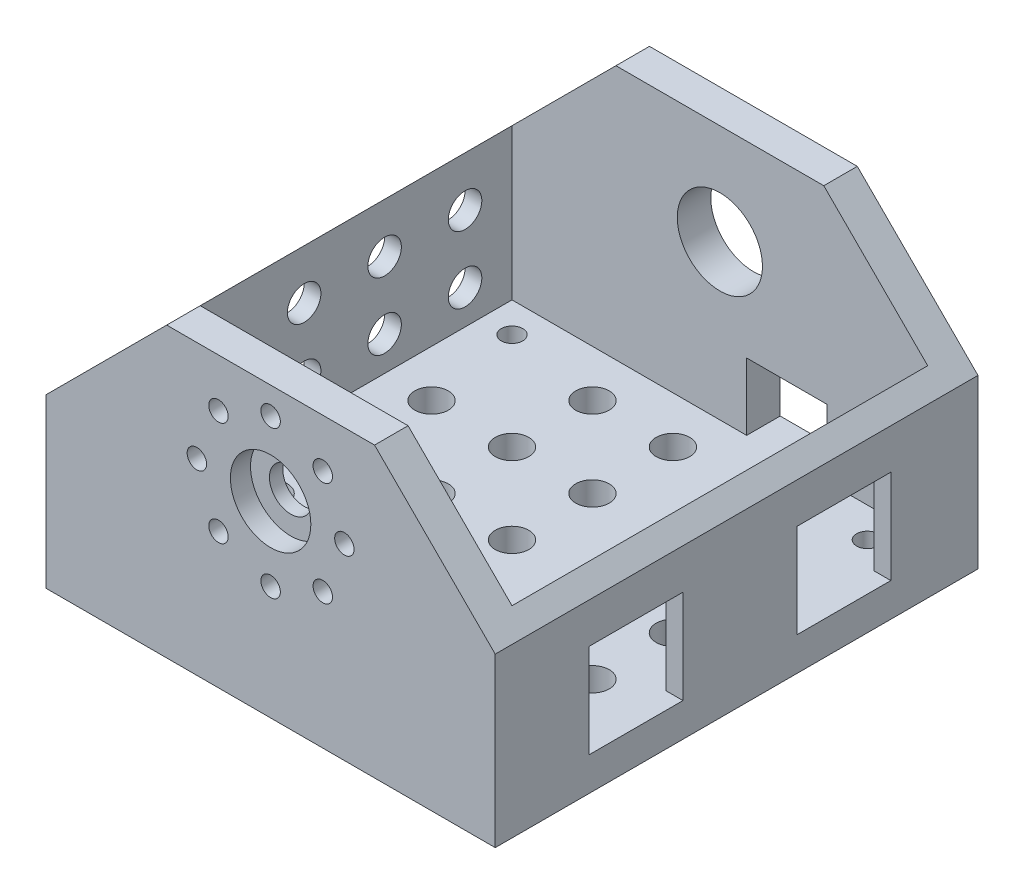
SolidWorks part; units mm, degrees
material "ABS"
ref_plane "Front Plane" through (0, 0, 0) normal (0, 0, 1) x (1, 0, 0)
ref_plane "Top Plane" through (0, 0, 0) normal (0, 1, 0) x (1, 0, 0)
ref_plane "Right Plane" through (0, 0, 0) normal (1, 0, 0) x (0, 0, -1)
sketch "Sketch1" plane through (0, 0, 0) normal (0, 1, 0) x (1, 0, 0)
  line L0 (-33.5, 36) -> (33.5, -36) construction
  line L1 (-33.5, 36) -> (33.5, 36)
  line L2 (-33.5, 36) -> (-33.5, -36)
  line L3 (-33.5, -36) -> (33.5, -36)
  line L4 (33.5, 36) -> (33.5, -36)
  point P4 (0, 0)
  dimension "D1" = 72
  dimension "D2" = 67
extrude "Boss-Extrude1" add sketch "Sketch1" along normal blind 43
sketch "Sketch2" plane through (0, 0, 36) normal (0, 0, 1) x (1, 0, 0)
  line L0 (-33.5, 43) -> (-33.5, 25)
  line L1 (-33.5, 43) -> (-33.5, 0) construction
  line L2 (-33.5, 25) -> (-15.5, 43)
  line L3 (-33.5, 43) -> (33.5, 43) construction
  line L4 (-15.5, 43) -> (-33.5, 43)
  line L5 (33.5, 43) -> (33.5, 25)
  line L6 (33.5, 43) -> (33.5, 0) construction
  line L7 (33.5, 25) -> (15.5, 43)
  line L8 (15.5, 43) -> (33.5, 43)
  dimension "D1" = 18
  dimension "D2" = 18
extrude "Cut-Extrude1" cut sketch "Sketch2" against normal through all
sketch "Sketch3" plane through (0, 43, 0) normal (0, 1, 0) x (1, 0, 0)
  line L0 (15.5, 36) -> (-15.5, 36) construction
  line L1 (-31, 31) -> (31, 31)
  line L2 (-31, 31) -> (-31, -31)
  line L3 (-31, -31) -> (31, -31)
  line L4 (31, 31) -> (31, -31)
  line L5 (-33.5, 36) -> (-33.5, -36) construction
  line L6 (33.5, 36) -> (33.5, -36) construction
  line L7 (-15.5, -36) -> (15.5, -36) construction
  dimension "D1" = 5
  dimension "D2" = 2.5
  dimension "D3" = 2.5
  dimension "D4" = 5
extrude "Cut-Extrude2" cut sketch "Sketch3" against normal blind 38
sketch "Sketch4" plane through (0, 0, -36) normal (0, 0, -1) x (-1, 0, 0)
  line L0 (0, 0) -> (0, 43) construction
  line L1 (-33.5, 0) -> (33.5, 0) construction
  line L2 (-15.5, 43) -> (15.5, 43) construction
  circle A0 centre (0, 28) radius 6.35
  dimension "D2" = 12.7
  dimension "D1" = 15
extrude "Cut-Extrude3" cut sketch "Sketch4" against normal up to next
sketch "Sketch5" plane through (0, 0, 36) normal (0, 0, 1) x (1, 0, 0)
  line L0 (0, 0) -> (0, 43) construction
  line L1 (-33.5, 0) -> (33.5, 0) construction
  line L2 (-15.5, 43) -> (15.5, 43) construction
  circle A0 centre (0, 28) radius 6
  dimension "D2" = 12
  dimension "D1" = 15
extrude "Cut-Extrude4" cut sketch "Sketch5" against normal blind 3
sketch "Sketch6" plane through (0, 0, 33) normal (0, 0, 1) x (1, 0, 0)
  circle A0 centre (0, 28) radius 3.175
  dimension "D1" = 6.35
extrude "Cut-Extrude5" cut sketch "Sketch6" against normal up to next
sketch "Sketch7" plane through (0, 0, 36) normal (0, 0, 1) x (1, 0, 0)
  line L0 (0, 0) -> (0, 43) construction
  line L1 (-33.5, 0) -> (33.5, 0) construction
  line L2 (-15.5, 43) -> (15.5, 43) construction
  circle A0 centre (0, 39) radius 1.45
  dimension "D2" = 2.9
  dimension "D1" = 4
extrude "Cut-Extrude6" cut sketch "Sketch7" against normal up to next
pattern_circular "CirPattern1" count 8 over 360 about axis through (0, 28, 33) along (0, 0, 1) of "Cut-Extrude6"
sketch "Sketch8" plane through (-33.5, 0, 0) normal (-1, 0, 0) x (0, 0, 1)
  line L0 (-36, 25) -> (36, 25) construction
  line L1 (-31, 27.5) -> (-31, 43) construction
  circle A0 centre (-24, 20.1) radius 2.5
  dimension "D1" = 5
  dimension "D2" = 4.9
  dimension "D3" = 7
extrude "Cut-Extrude7" cut sketch "Sketch8" against normal up to next
pattern_linear "Front Vent" count 5 spacing 12 along (0, 0, 1) count 2 spacing 10 along (0, -1, 0) of "Cut-Extrude7"
sketch "Sketch10" plane through (0, 5, 0) normal (0, 1, 0) x (1, 0, 0)
  line L0 (31, 31) -> (-31, 31) construction
  line L1 (-31, 31) -> (-31, -31) construction
  line L2 (-24, 24) -> (-12, 24) construction
  line L3 (-24, 24) -> (-24, 12) construction
  circle A0 centre (-24, 24) radius 2.5
  circle A1 centre (-12, 24) radius 2.5
  circle A2 centre (0, 24) radius 2.5
  circle A3 centre (12, 24) radius 2.5
  circle A4 centre (24, 24) radius 2.5
  circle A5 centre (-12, 12) radius 2.5
  circle A6 centre (0, 12) radius 2.5
  circle A7 centre (12, 12) radius 2.5
  circle A8 centre (24, 12) radius 2.5
  circle A9 centre (-12, 0) radius 2.5
  circle A10 centre (0, 0) radius 2.5
  circle A11 centre (12, 0) radius 2.5
  circle A12 centre (24, 0) radius 2.5
  circle A13 centre (-12, -12) radius 2.5
  circle A14 centre (0, -12) radius 2.5
  circle A15 centre (12, -12) radius 2.5
  circle A16 centre (24, -12) radius 2.5
  circle A17 centre (-12, -24) radius 2.5
  circle A18 centre (0, -24) radius 2.5
  circle A19 centre (12, -24) radius 2.5
  circle A20 centre (24, -24) radius 2.5
  circle A21 centre (-24, 12) radius 2.5
  circle A22 centre (-24, 0) radius 2.5
  circle A23 centre (-24, -12) radius 2.5
  circle A24 centre (-24, -24) radius 2.5
  dimension "D1" = 5
  dimension "D2" = 7
  dimension "D3" = 7
  dimension "D6" = 12
  dimension "D7" = 12
  dimension "D4" = 5
  dimension "D5" = 5
extrude "Bottom Vent" cut sketch "Sketch10" against normal up to next contours A1 | A5 | A21 | A22 | A9 | A13 | A23 | A17 | A18 | A14 | A15 | A19 | A16 | A11 | A10 | A6 | A7 | A8 | A3 | A2 | A12 | A21 region at (-12, 5, -24) region at (0, 5, -24) region at (12, 5, -24) region at (-12, 5, -12) region at (0, 5, -12) region at (12, 5, -12) region at (24, 5, -12) region at (-12, 5, 0) region at (0, 5, 0) region at (12, 5, 0) region at (24, 5, 0) region at (-12, 5, 12) region at (0, 5, 12) region at (12, 5, 12) region at (24, 5, 12) region at (-12, 5, 24) region at (0, 5, 24) region at (12, 5, 24) region at (-24, 5, -12) region at (-24, 5, 0) region at (-24, 5, 12)
sketch "Sketch12" plane through (0, 5, 0) normal (0, 1, 0) x (1, 0, 0)
  line L0 (31, 31) -> (-31, 31) construction
  line L1 (-31, 31) -> (-31, -31) construction
  line L2 (31, -31) -> (31, 31) construction
  line L3 (-26.5, 26.5) -> (26.5, 26.5) construction
  line L4 (-26.5, 26.5) -> (-26.5, -26.5) construction
  line L5 (-26.5, -26.5) -> (26.5, -26.5) construction
  line L6 (26.5, 26.5) -> (26.5, -26.5) construction
  line L7 (-31, -31) -> (31, -31) construction
  circle A0 centre (-26.5, 26.5) radius 1.6
  circle A2 centre (26.5, 26.5) radius 1.6
  circle A3 centre (-26.5, -26.5) radius 1.6
  circle A4 centre (26.5, -26.5) radius 1.6
  dimension "D1" = 3.2
  dimension "D6" = 3.2
  dimension "D7" = 3.2
  dimension "D8" = 3.2
  dimension "D2" = 4.5
  dimension "D3" = 4.5
  dimension "D4" = 4.5
  dimension "D5" = 4.5
extrude "Mounting Holes" cut sketch "Sketch12" against normal through all
sketch "Sketch13" plane through (33.5, 0, 0) normal (1, 0, 0) x (0, 0, -1)
  line L0 (36, 25) -> (36, 0) construction
  line L1 (-22, 19) -> (-8, 19)
  line L2 (-22, 19) -> (-22, 5)
  line L3 (-22, 5) -> (-8, 5)
  line L4 (-8, 19) -> (-8, 5)
  line L5 (9, 19) -> (23, 19)
  line L6 (9, 19) -> (9, 5)
  line L7 (9, 5) -> (23, 5)
  line L8 (23, 19) -> (23, 5)
  line L9 (-36, 0) -> (36, 0) construction
  dimension "D1" = 13
  dimension "D2" = 14
  dimension "D3" = 17
  dimension "D4" = 14
  dimension "D5" = 14
  dimension "D6" = 5
extrude "Cut-Extrude12" cut sketch "Sketch13" against normal up to next
sketch "Sketch14" plane through (0, 0, -36) normal (0, 0, -1) x (-1, 0, 0)
  line L0 (-33.5, 0) -> (33.5, 0) construction
  line L1 (-16, 15) -> (-4, 15)
  line L2 (-16, 15) -> (-16, 5)
  line L3 (-16, 5) -> (-4, 5)
  line L4 (-4, 15) -> (-4, 5)
  line L5 (-33.5, 25) -> (-33.5, 0) construction
  dimension "D1" = 5
  dimension "D2" = 10
  dimension "D3" = 12
  dimension "D4" = 17.5
extrude "Cut-Extrude13" cut sketch "Sketch14" against normal up to next
